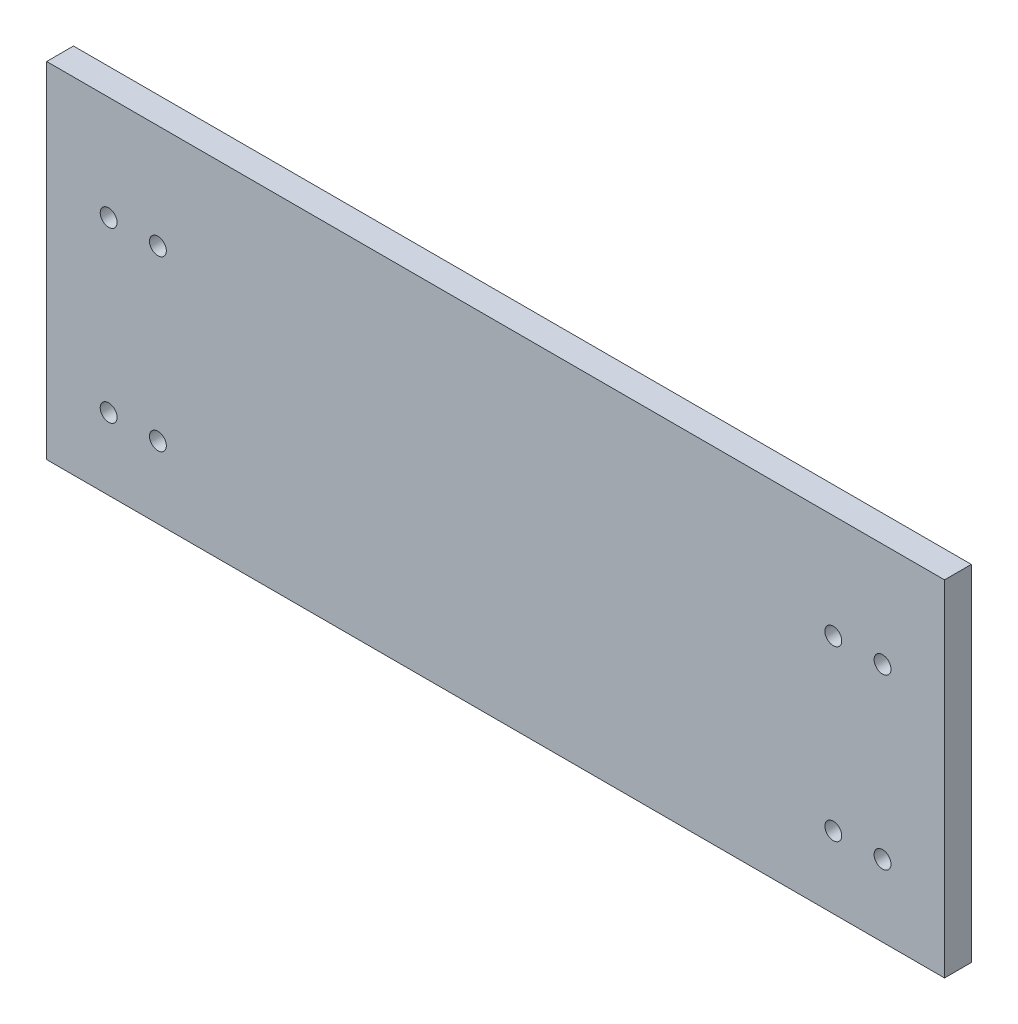
SolidWorks part; units mm, degrees
ref_plane "Front Plane" through (0, 0, 0) normal (0, 0, 1) x (1, 0, 0)
ref_plane "Top Plane" through (0, 0, 0) normal (0, 1, 0) x (1, 0, 0)
ref_plane "Right Plane" through (0, 0, 0) normal (1, 0, 0) x (0, 0, -1)
sketch "Sketch1" plane through (0, 0, 0) normal (0, 0, 1) x (1, 0, 0)
  line L1 (319.05, 19.05) -> (-319.05, 19.05)
  line L2 (319.05, 19.05) -> (319.05, -226)
  line L3 (319.05, -226) -> (-319.05, -226)
  line L4 (-319.05, 19.05) -> (-319.05, -226)
  dimension "D1" = 245.05
  dimension "D2" = 638.1
extrude "Boss-Extrude1" add sketch "Sketch1" along normal blind 19.05
sketch "Sketch5" plane through (0, 0, 19.05) normal (0, 0, 1) x (1, 0, 0)
  circle A0 centre (-275, -175) radius 9.017 construction
  circle A1 centre (-275, -55) radius 9.017 construction
  circle A2 centre (-240, -55) radius 9.017 construction
  circle A3 centre (-240, -175) radius 9.017 construction
  circle A4 centre (275, -55) radius 9.017 construction
  circle A5 centre (240, -55) radius 9.017 construction
  circle A6 centre (240, -175) radius 9.017 construction
  circle A7 centre (275, -175) radius 9.017 construction
  circle A8 centre (-275, -175) radius 9.017
  circle A9 centre (-275, -55) radius 9.017
  circle A10 centre (-240, -55) radius 9.017
  circle A11 centre (-240, -175) radius 9.017
  circle A12 centre (275, -55) radius 9.017
  circle A13 centre (240, -55) radius 9.017
  circle A14 centre (240, -175) radius 9.017
  circle A15 centre (275, -175) radius 9.017
hole_wizard "Ø12.0mm Dowel Hole1" positions "Sketch6" profile "Sketch7" hole size "Ø12.0" standard "ANSI Metric"
sketch "Sketch6" plane through (0, 0, 19.05) normal (0, 0, 1) x (1, 0, 0)
  point P0 (275, -175)
  point P3 (275, -55)
  point P6 (240, -175)
  point P9 (240, -55)
  point P12 (-275, -175)
  point P15 (-240, -175)
  point P18 (-240, -55)
  point P21 (-275, -55)
sketch "Sketch7" plane through (275, -175, 19.05) normal (1, 0, 0) x (0, -1, 0)
  line L0 (0, 0) -> (0, 30)
  line L1 (0, 30) -> (6, 26.3948)
  line L2 (6, 26.3948) -> (6, 0)
  line L5 (6, 0) -> (0, 0)
  line L10 (0, 30) -> (-6, 26.3948) construction
  line L11 (0, -6.35) -> (0, 107.95) construction
  dimension "Hole Dia." = 12
  dimension "Hole Depth" = 30
  dimension "Drill Angle" = 118
